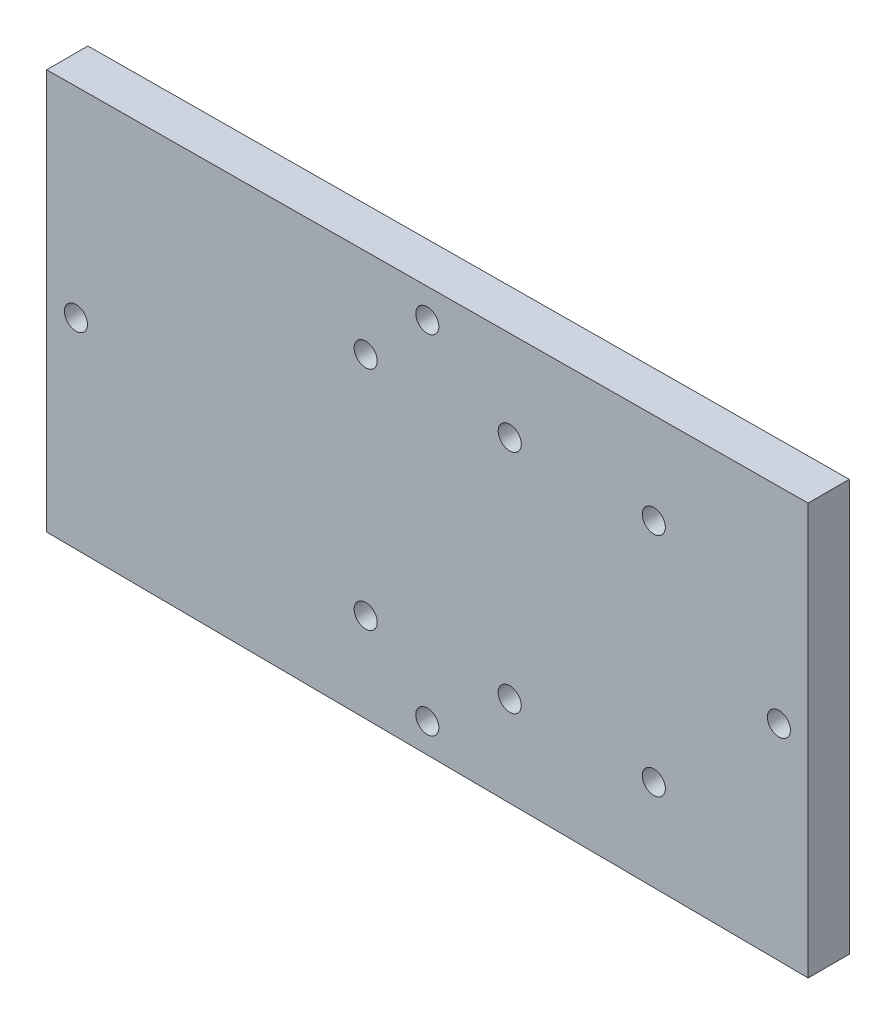
SolidWorks part; units mm, degrees
other "Markup1"
sketch "Sketch1" plane through (-469.9, -139.6094, 0) normal (0, 0, 1) x (-1, 0, 0)
material "Custom Plastic"
ref_plane "X-Y Datum" through (0, 0, 0) normal (0, 0, 1) x (1, 0, 0)
ref_plane "X-Z Datum" through (0, 0, 0) normal (0, 1, 0) x (1, 0, 0)
ref_plane "Y-Z Datum" through (0, 0, 0) normal (1, 0, 0) x (0, 0, -1)
sketch "Pedal Box Floor" plane through (0, 0, 0) normal (0, 0, 1) x (1, 0, 0)
  line L0 (0, -126.9088) -> (-469.9, -123.5566)
  line L8 (0, -139.6094) -> (-469.9, -136.2572) construction
  line L9 (0, 0) -> (-469.9, 0) construction
  line L10 (-234.95, -137.9333) -> (-234.8594, -125.2333) construction
  line L11 (-469.9, 123.5566) -> (-469.9, -123.5566)
  line L12 (0, 126.9088) -> (0, -126.9088)
  line L13 (0, -139.6094) -> (0, -126.9088) construction
  line L14 (-469.9, -136.2572) -> (-469.9, -123.5566) construction
  line L15 (-469.9, 136.2572) -> (-469.9, 123.5566) construction
  line L16 (-234.95, 137.9333) -> (-234.8594, 125.2333) construction
  line L17 (0, 126.9088) -> (-469.9, 123.5566)
  line L18 (0, 139.6094) -> (-469.9, 136.2572) construction
  line L19 (0, 139.6094) -> (0, 126.9088) construction
  line L20 (-95.25, -69.85) -> (-184.15, -69.85) construction
  line L21 (-184.15, -69.85) -> (-273.05, -69.85) construction
  line L22 (-96.52, -86.36) -> (-184.15, -86.36) construction
  line L23 (-96.52, -53.34) -> (-184.15, -53.34) construction
  line L24 (-95.25, -77.3634) -> (-95.25, -85.09) construction
  line L25 (-95.25, -62.3366) -> (-95.25, -54.61) construction
  line L26 (-184.15, -86.36) -> (-184.15, -53.34) construction
  line L27 (-271.78, -53.34) -> (-184.15, -53.34) construction
  line L28 (-273.05, -62.3366) -> (-273.05, -54.61) construction
  line L29 (-273.05, -77.3634) -> (-273.05, -85.09) construction
  line L30 (-271.78, -86.36) -> (-184.15, -86.36) construction
  line L31 (-273.05, 77.3634) -> (-273.05, 85.09) construction
  line L32 (-273.05, 62.3366) -> (-273.05, 54.61) construction
  line L33 (-271.78, 53.34) -> (-184.15, 53.34) construction
  line L34 (-271.78, 86.36) -> (-184.15, 86.36) construction
  line L35 (-96.52, 53.34) -> (-184.15, 53.34) construction
  line L36 (-95.25, 62.3366) -> (-95.25, 54.61) construction
  line L37 (-96.52, 86.36) -> (-184.15, 86.36) construction
  line L38 (-95.25, 77.3634) -> (-95.25, 85.09) construction
  circle A0 centre (-95.25, -69.85) radius 7.1247
  circle A1 centre (-184.15, -69.85) radius 7.1247
  circle A2 centre (-273.05, -69.85) radius 7.1247
  arc A3 (-94.1917, -76.1112) -> (-94.1917, -63.5888) centre (-95.25, -69.85) ccw construction
  arc A4 (-96.52, -53.34) -> (-95.25, -54.61) centre (-96.52, -54.61) cw construction
  arc A5 (-95.25, -85.09) -> (-96.52, -86.36) centre (-96.52, -85.09) cw construction
  arc A6 (-95.25, -62.3366) -> (-94.1917, -63.5888) centre (-93.98, -62.3366) ccw construction
  arc A7 (-94.1917, -76.1112) -> (-95.25, -77.3634) centre (-93.98, -77.3634) ccw construction
  arc A8 (-271.78, -53.34) -> (-273.05, -54.61) centre (-271.78, -54.61) ccw construction
  arc A9 (-273.05, -62.3366) -> (-274.1083, -63.5888) centre (-274.32, -62.3366) cw construction
  arc A10 (-274.1083, -76.1112) -> (-274.1083, -63.5888) centre (-273.05, -69.85) cw construction
  arc A11 (-274.1083, -76.1112) -> (-273.05, -77.3634) centre (-274.32, -77.3634) cw construction
  arc A12 (-273.05, -85.09) -> (-271.78, -86.36) centre (-271.78, -85.09) ccw construction
  circle A13 centre (-273.05, 69.85) radius 7.1247
  arc A14 (-274.1083, 76.1112) -> (-273.05, 77.3634) centre (-274.32, 77.3634) ccw construction
  arc A15 (-274.1083, 76.1112) -> (-274.1083, 63.5888) centre (-273.05, 69.85) ccw construction
  arc A16 (-273.05, 62.3366) -> (-274.1083, 63.5888) centre (-274.32, 62.3366) ccw construction
  arc A17 (-271.78, 53.34) -> (-273.05, 54.61) centre (-271.78, 54.61) cw construction
  arc A18 (-273.05, 85.09) -> (-271.78, 86.36) centre (-271.78, 85.09) cw construction
  circle A19 centre (-184.15, 69.85) radius 7.1247
  arc A20 (-96.52, 53.34) -> (-95.25, 54.61) centre (-96.52, 54.61) ccw construction
  arc A21 (-95.25, 62.3366) -> (-94.1917, 63.5888) centre (-93.98, 62.3366) cw construction
  arc A22 (-95.25, 85.09) -> (-96.52, 86.36) centre (-96.52, 85.09) ccw construction
  arc A23 (-94.1917, 76.1112) -> (-95.25, 77.3634) centre (-93.98, 77.3634) cw construction
  arc A24 (-94.1917, 76.1112) -> (-94.1917, 63.5888) centre (-95.25, 69.85) cw construction
  circle A25 centre (-95.25, 69.85) radius 7.1247
  circle A26 centre (-273.05, 69.85) radius 7.1247
  circle A27 centre (-184.15, 69.85) radius 7.1247
  circle A28 centre (-95.25, 69.85) radius 7.1247
  circle A29 centre (-95.25, -69.85) radius 7.1247
  circle A30 centre (-184.15, -69.85) radius 7.1247
  circle A31 centre (-273.05, -69.85) radius 7.1247
  point P6 (-234.95, -137.9333)
  point P49 (-88.9, -69.85)
  dimension "D4" = 14.2494
  dimension "D7" = 6.35
  dimension "D8" = 1.27
  dimension "D1" = 12.7
  dimension "D2" = 469.9
  dimension "D3" = 90.409
  dimension "D5" = 126.9088
  dimension "D6" = 88.9
  dimension "D9" = 95.25
  dimension "D10" = 69.85
  dimension "D11" = 33.02
  dimension "D12" = 88.9
sketch "Sketch2" plane through (0, 0, 0) normal (0, 0, 1) x (1, 0, 0)
  line L0 (0, 0) -> (-469.9, 0) construction
  line L1 (-184.15, -86.36) -> (-184.15, -53.34) construction
  circle A0 centre (-235.0266, -107.2001) radius 7.1247
  circle A1 centre (-235.0266, 107.1993) radius 7.1247
  circle A2 centre (-18.034, 0) radius 7.1247
  circle A3 centre (-451.866, 0) radius 7.1247
  circle A4 centre (-273.05, -69.85) radius 7.1247
  circle A5 centre (-184.15, -69.85) radius 7.1247
  circle A6 centre (-95.25, -69.85) radius 7.1247
  circle A7 centre (-95.25, 69.85) radius 7.1247
  circle A8 centre (-184.15, 69.85) radius 7.1247
  circle A9 centre (-273.05, 69.85) radius 7.1247
  dimension "D1" = 18.034
  dimension "D2" = 18.034
  dimension "D3" = 18.034
  dimension "D4" = 18.034
extrude "Boss-Extrude2" add sketch "Pedal Box Floor" along normal blind 25.4 contours L12 L0 L11 L17
extrude "Cut-Extrude1" cut sketch "Sketch2" along normal blind 25.4 contours A1
extrude "Cut-Extrude2" cut sketch "Sketch2<3>" along normal blind 25.4 contours A2
sketch "Sketch2<3>" plane through (0, 0, 0) normal (0, 0, 1) x (1, 0, 0) same geometry as "Sketch2"
extrude "Cut-Extrude3" cut sketch "Sketch2<4>" along normal blind 25.4 contours A3
sketch "Sketch2<4>" plane through (0, 0, 0) normal (0, 0, 1) x (1, 0, 0) same geometry as "Sketch2"
extrude "Cut-Extrude4" cut sketch "Sketch2<5>" along normal blind 25.4 contours A0
sketch "Sketch2<5>" plane through (0, 0, 0) normal (0, 0, 1) x (1, 0, 0) same geometry as "Sketch2"
extrude "Cut-Extrude5" cut sketch "Sketch2<6>" along normal blind 25.4 contours A4
sketch "Sketch2<6>" plane through (0, 0, 0) normal (0, 0, 1) x (1, 0, 0) same geometry as "Sketch2"
extrude "Cut-Extrude6" cut sketch "Sketch2<7>" along normal blind 25.4 contours A5
sketch "Sketch2<7>" plane through (0, 0, 0) normal (0, 0, 1) x (1, 0, 0) same geometry as "Sketch2"
extrude "Cut-Extrude7" cut sketch "Sketch2<8>" along normal blind 25.4 contours A6
sketch "Sketch2<8>" plane through (0, 0, 0) normal (0, 0, 1) x (1, 0, 0) same geometry as "Sketch2"
extrude "Cut-Extrude8" cut sketch "Sketch2<9>" along normal blind 25.4 contours A9
sketch "Sketch2<9>" plane through (0, 0, 0) normal (0, 0, 1) x (1, 0, 0) same geometry as "Sketch2"
extrude "Cut-Extrude9" cut sketch "Sketch2<10>" along normal blind 25.4 contours A8
sketch "Sketch2<10>" plane through (0, 0, 0) normal (0, 0, 1) x (1, 0, 0) same geometry as "Sketch2"
extrude "Cut-Extrude10" cut sketch "Sketch2<11>" along normal blind 25.4 contours A7
sketch "Sketch2<11>" plane through (0, 0, 0) normal (0, 0, 1) x (1, 0, 0) same geometry as "Sketch2"
